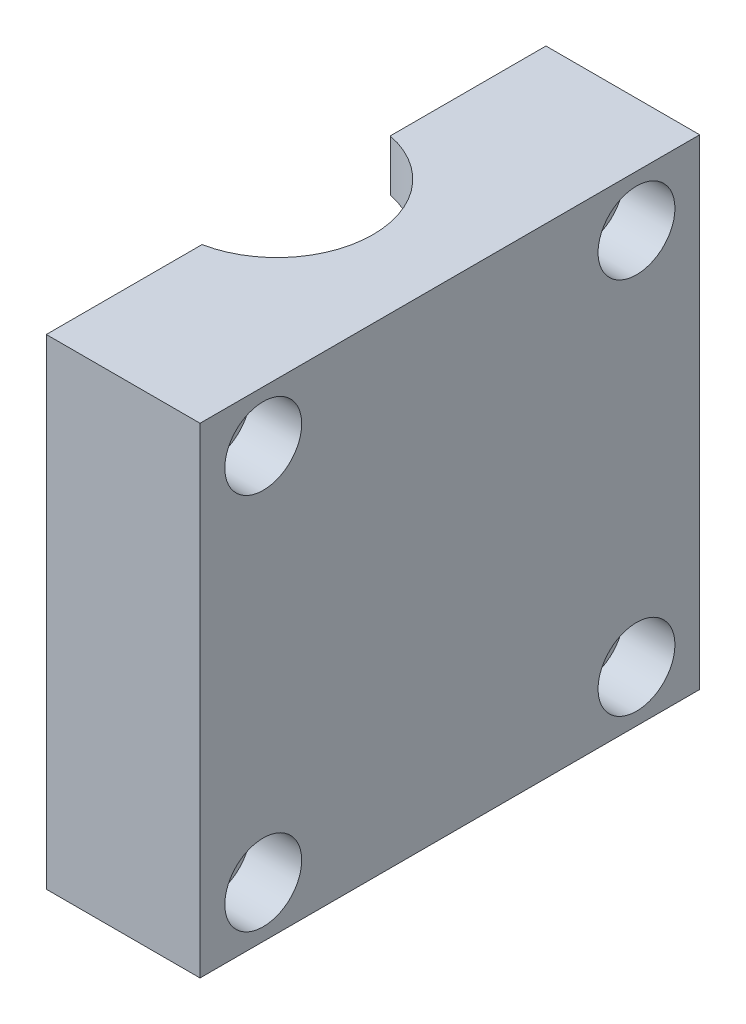
SolidWorks part; units mm, degrees
ref_plane "Plan de face" through (0, 0, 0) normal (0, 0, 1) x (1, 0, 0)
ref_plane "Plan de dessus" through (0, 0, 0) normal (0, 1, 0) x (1, 0, 0)
ref_plane "Plan de droite" through (0, 0, 0) normal (1, 0, 0) x (0, 0, -1)
sketch "Esquisse1" plane through (0, 0, 0) normal (0, 1, 0) x (1, 0, 0)
  line L0 (0, 18.2074) -> (0, 19.5) construction
  line L1 (0, 0) -> (12, 0) construction
  line L2 (0, 0) -> (0, 39) construction
  line L3 (0, 39) -> (12, 39) construction
  line L4 (12, 0) -> (12, 39) construction
  line L5 (0, 19.5) -> (-1.5, 19.5) construction
  line L6 (0, 29.1339) -> (0, 39)
  line L7 (0, 39) -> (12, 39)
  line L8 (12, 39) -> (12, 0)
  line L9 (12, 0) -> (0, 0)
  line L10 (0, 0) -> (0, 9.8661)
  circle A0 centre (-1.5, 19.5) radius 9.75 construction
  arc A1 (0, 29.1339) -> (0, 9.8661) centre (-1.5, 19.5) cw
  dimension "D4" = 19.5
  dimension "D1" = 39
  dimension "D2" = 12
  dimension "D3" = 1.5
extrude "Boss.-Extru.1" add sketch "Esquisse1" along normal blind 37.5
sketch "Esquisse2" plane through (0, 0, 0) normal (0, -1, 0) x (1, 0, 0)
  line L0 (0, 0) -> (0, -39) construction
  line L1 (0, -19.5) -> (-1.5, -19.5) construction
  line L2 (0, -12.1515) -> (0, 0) construction
  line L3 (0, 0) -> (12, 0)
  line L4 (12, 0) -> (12, -39)
  line L5 (12, -39) -> (0, -39)
  line L6 (0, -39) -> (0, -26.8485) construction
  line L7 (0, -26.8485) -> (0, -39)
  line L8 (0, 0) -> (0, -12.1515)
  circle A0 centre (-1.5, -19.5) radius 7.5 construction
  arc A1 (0, -12.1515) -> (0, -26.8485) centre (-1.5, -19.5) cw
  dimension "D2" = 15
  dimension "D1" = 1.5
extrude "Boss.-Extru.2" add sketch "Esquisse2" against normal blind 4
ref_plane "Plan1" through (0, 18.75, 0) normal (0, 1, 0) x (1, 0, 0)
mirror "Symétrie1" about plane through (0, 18.75, 0) normal (0, 1, 0) of "Boss.-Extru.2"
sketch "Esquisse3" plane through (0, 0, 0) normal (-1, 0, 0) x (0, 0, 1)
  line L0 (-29.1339, 33.5) -> (-39, 33.5) construction
  line L1 (-39, 37.5) -> (-39, 0) construction
  line L2 (-19.5, 37.5) -> (-19.5, 0) construction
  line L3 (-12.1515, 37.5) -> (-26.8485, 37.5) construction
  line L4 (-26.8485, 0) -> (-12.1515, 0) construction
  line L5 (-39, 18.75) -> (0, 18.75) construction
  line L6 (0, 37.5) -> (0, 0) construction
  circle A0 centre (-34.067, 33.5) radius 2
  circle A1 centre (-34.067, 4) radius 2
  circle A2 centre (-4.933, 4) radius 2
  circle A3 centre (-4.933, 33.5) radius 2
  dimension "D1" = 4
extrude "Enlèv. mat.-Extru.1" cut sketch "Esquisse3" against normal through all
sketch "Esquisse5" plane through (12, 0, 0) normal (1, 0, 0) x (0, 0, -1)
  circle A0 centre (4.933, 33.5) radius 3
  circle A1 centre (34.067, 33.5) radius 3
  circle A2 centre (34.067, 4) radius 3
  circle A3 centre (4.933, 4) radius 3
  dimension "D1" = 6
extrude "Enlèv. mat.-Extru.2" cut sketch "Esquisse5" against normal blind 4
